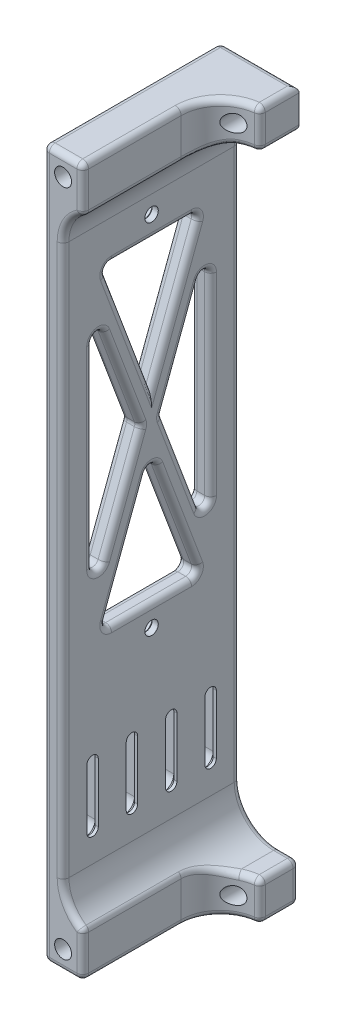
SolidWorks part; units mm, degrees
ref_plane "Front Plane" through (0, 0, 0) normal (0, 0, 1) x (1, 0, 0)
ref_plane "Top Plane" through (0, 0, 0) normal (0, 1, 0) x (1, 0, 0)
ref_plane "Right Plane" through (0, 0, 0) normal (1, 0, 0) x (0, 0, -1)
sketch "Sketch1" plane through (0, 0, 0) normal (1, 0, 0) x (0, 0, -1)
  line L1 (0, 0) -> (45, 0)
  line L2 (0, 0) -> (0, 180)
  line L3 (0, 180) -> (45, 180)
  line L4 (45, 0) -> (45, 180)
  dimension "D1" = 45
  dimension "D2" = 180
extrude "Boss-Extrude1" add sketch "Sketch1" along normal blind 10
sketch "Sketch2" plane through (10, 0, 0) normal (1, 0, 0) x (0, 0, -1)
  line L0 (0, 110) -> (45, 110) construction
  line L1 (0, 0) -> (45, 0) construction
  line L3 (22.5, 64.5) -> (22.5, 155.5) construction
  line L4 (0, 180) -> (0, 0) construction
  line L5 (45, 0) -> (45, 180) construction
  line L6 (27.5, 110) -> (17.5, 110) construction
  point P7 (22.5, 155.5)
  point P8 (22.5, 64.5)
  point P9 (22.5, 110)
  dimension "D1" = 91
  dimension "D2" = 110
  dimension "D3" = 10
hole_wizard "M3 Clearance Hole1" positions "Sketch2" profile "Sketch4" hole size "M3" standard "ANSI Metric"
sketch "Sketch4" plane through (10, 64.5, -22.5) normal (0, 1, 0) x (0, 0, -1)
  line L0 (0, 0) -> (0, 10)
  line L1 (0, 10) -> (1.7, 10)
  line L2 (1.7, 10) -> (1.7, 0)
  line L5 (1.7, 0) -> (0, 0)
  line L11 (0, -6.35) -> (0, 107.95) construction
  dimension "Thru Hole Dia." = 3.4
  dimension "Thru Hole Depth" = 10
sketch "Sketch5" plane through (10, 0, 0) normal (1, 0, 0) x (0, 0, -1)
  line L0 (45, 180) -> (0, 180) construction
  line L1 (45, 180) -> (35, 180)
  line L2 (45, 180) -> (45, 170)
  line L3 (45, 170) -> (35, 170)
  line L4 (35, 180) -> (35, 170)
  line L5 (0, 180) -> (10, 180)
  line L6 (0, 180) -> (0, 170)
  line L7 (0, 170) -> (10, 170)
  line L8 (10, 180) -> (10, 170)
  line L9 (0, 0) -> (45, 0) construction
  line L10 (0, 0) -> (10, 0)
  line L11 (0, 0) -> (0, 10)
  line L12 (0, 10) -> (10, 10)
  line L13 (10, 0) -> (10, 10)
  line L14 (45, 0) -> (35, 0)
  line L15 (45, 0) -> (45, 10)
  line L16 (45, 10) -> (35, 10)
  line L17 (35, 0) -> (35, 10)
  line L18 (45, 0) -> (45, 180) construction
  line M18 (0, 0) -> (45, 0)
  line M19 (45, 0) -> (45, 180)
  line M20 (45, 180) -> (0, 180)
  dimension "D1" = 10
  dimension "D2" = 10
  dimension "D3" = 10
  dimension "D4" = 10
  dimension "D5" = 10
  dimension "D6" = 10
  dimension "D7" = 10
  dimension "D8" = 10
extrude "Boss-Extrude2" add sketch "Sketch5" along normal blind 10 contours L4 L3 M20 M19 | L17 L16 M18 M19
fillet "Fillet1" radius 10 2 edges at (10, 5, -35) (10, 175, -35)
sketch "Sketch7" plane through (0, 0, -45) normal (0, 0, -1) x (-1, 0, 0)
  line L0 (-15, 175) -> (-5, 175) construction
  line L1 (-5, 175) -> (-5, 5) construction
  line L2 (-5, 5) -> (-15, 5) construction
  line L4 (0, 0) -> (0, 180) construction
  line L5 (-20, 10) -> (-10, 10) construction
  line L7 (-20, 180) -> (0, 180) construction
  line L8 (-20, 0) -> (-20, 10) construction
  line L9 (-20, 170) -> (-20, 180) construction
  point P0 (-15, 175)
  point P1 (-5, 175)
  point P3 (-5, 5)
  point P4 (-15, 5)
  dimension "D1" = 5
  dimension "D2" = 5
  dimension "D3" = 5
  dimension "D4" = 5
  dimension "D5" = 5
hole_wizard "Ø4.3 (4.3) Diameter Hole1" positions "Sketch7" profile "Sketch8" hole size "Ø4.3" standard "ANSI Metric" end condition through all
sketch "Sketch8" plane through (15, 175, -45) normal (1, 0, 0) x (0, 1, 0)
  line L0 (0, 0) -> (0, 45)
  line L1 (0, 45) -> (2.15, 45)
  line L2 (2.15, 45) -> (2.15, 0)
  line L5 (2.15, 0) -> (0, 0)
  line L11 (0, -6.35) -> (0, 107.95) construction
  dimension "Thru Hole Dia." = 4.3
  dimension "Thru Hole Depth" = 45
sketch "Sketch9" plane through (10, 0, 0) normal (1, 0, 0) x (0, 0, -1)
  line L0 (0, 180) -> (0, 0) construction
  line L1 (0, 170) -> (45, 170)
  line L2 (0, 170) -> (0, 10)
  line L3 (0, 10) -> (45, 10)
  line L4 (45, 170) -> (45, 10)
  line L6 (0, 180) -> (0, 0) construction
  point P6 (0, 166.7431)
  point P9 (0, 0)
  point P11 (45, 170)
  point P13 (0, 0)
  point P14 (45, 10)
extrude "Cut-Extrude1" cut sketch "Sketch9" against normal blind 5
sketch "Sketch10" plane through (5, 0, 0) normal (1, 0, 0) x (0, 0, -1)
  line L0 (0, 110) -> (45, 110) construction
  line L3 (7.5, 150) -> (37.5, 70) construction
  line L4 (7.5, 150) -> (37.5, 150)
  line L5 (7.5, 150) -> (7.5, 70)
  line L6 (7.5, 70) -> (37.5, 70)
  line L7 (37.5, 150) -> (37.5, 70)
  line L8 (7.5, 150) -> (37.5, 70) construction
  line L9 (7.5, 70) -> (37.5, 150) construction
  line L10 (9.8408, 150.8778) -> (39.8408, 70.8778)
  line L11 (5.1592, 149.1222) -> (35.1592, 69.1222)
  line L12 (37.5, 150) -> (7.5, 70) construction
  line L13 (39.8408, 149.1222) -> (9.8408, 69.1222)
  line L14 (35.1592, 150.8778) -> (5.1592, 70.8778)
  line L15 (22.5, 155.5) -> (22.5, 64.5) construction
  arc A0 (9.8408, 150.8778) -> (5.1592, 149.1222) centre (7.5, 150) ccw
  arc A1 (35.1592, 69.1222) -> (39.8408, 70.8778) centre (37.5, 70) ccw
  arc A2 (39.8408, 149.1222) -> (35.1592, 150.8778) centre (37.5, 150) ccw
  arc A3 (5.1592, 70.8778) -> (9.8408, 69.1222) centre (7.5, 70) ccw
  point P2 (22.5, 110)
  point P6 (22.5, 110)
  point P11 (22.5, 110)
  point P16 (22.5, 110)
  dimension "D1" = 30
  dimension "D2" = 80
  dimension "D3" = 5
  dimension "D4" = 5
extrude "Cut-Extrude2" cut sketch "Sketch10" against normal blind 5 contours L14 L4 L10 | L14 L11 L5 | L11 L13 L6 | L7 L13 L10
fillet "Fillet2" radius 10 2 edges at (5, 10, -22.5) (5, 170, -22.5)
sketch "Sketch11" plane through (0, 0, 0) normal (-1, 0, 0) x (0, 0, 1)
  point P0 (-22.5, 155.5)
  point P1 (-22.5, 64.5)
hole_wizard "Ø4.3 (4.3) Diameter Hole2" positions "Sketch11" profile "Sketch12" hole size "Ø4.3" standard "ANSI Metric"
sketch "Sketch12" plane through (0, 155.5, -22.5) normal (0, 1, 0) x (0, 0, 1)
  line L0 (0, 0) -> (0, 3)
  line L1 (0, 3) -> (2.15, 3)
  line L2 (2.15, 3) -> (2.15, 0)
  line L5 (2.15, 0) -> (0, 0)
  line L10 (0, 3) -> (-2.15, 3) construction
  line L11 (0, -6.35) -> (0, 107.95) construction
  dimension "Hole Dia." = 4.3
  dimension "Hole Depth" = 3
  dimension "Drill Angle" = 180
chamfer "Chamfer1" distance 0.45 angle 45 2 edges at (3, 64.5, -24.2) (3, 155.5, -24.2)
sketch "Sketch13" plane through (5, 0, 0) normal (1, 0, 0) x (0, 0, -1)
  line L0 (7.5, 42.5) -> (7.5, 27.5) construction
  line L1 (8.95, 42.5) -> (8.95, 27.5)
  line L2 (6.05, 42.5) -> (6.05, 27.5)
  line L3 (0, 160) -> (0, 20) construction
  line L4 (0, 0) -> (25, 0) construction
  arc A0 (8.95, 42.5) -> (6.05, 42.5) centre (7.5, 42.5) ccw
  arc A1 (6.05, 27.5) -> (8.95, 27.5) centre (7.5, 27.5) ccw
  point P2 (7.5, 35)
  dimension "D1" = 1.45
  dimension "D2" = 15
  dimension "D3" = 7.5
  dimension "D4" = 35
extrude "Cut-Extrude3" cut sketch "Sketch13" against normal blind 5
pattern_linear "LPattern1" count 4 spacing 10 along (0, 0, -1) of "Cut-Extrude3"
sketch "Sketch14" plane through (0, 0, 0) normal (-1, 0, 0) x (0, 0, 1)
  line L9 (-34.85, 27.5) -> (-34.85, 42.5)
  line L10 (-40.15, 42.5) -> (-40.15, 27.5)
  line L11 (-34.85, 27.5) -> (-34.85, 42.5)
  line L12 (-40.15, 42.5) -> (-40.15, 27.5)
  arc A5 (-40.15, 27.5) -> (-34.85, 27.5) centre (-37.5, 27.5) ccw
  arc A6 (-34.85, 42.5) -> (-40.15, 42.5) centre (-37.5, 42.5) ccw
  arc A7 (-40.15, 27.5) -> (-34.85, 27.5) centre (-37.5, 27.5) ccw
  arc A8 (-34.85, 42.5) -> (-40.15, 42.5) centre (-37.5, 42.5) ccw
  dimension "D1" = 1.2
extrude "Cut-Extrude4" cut sketch "Sketch14" against normal blind 3
pattern_linear "LPattern2" count 4 spacing 10 along (0, 0, 1) of "Cut-Extrude4"
chamfer "Chamfer2" distance 1.2 angle 45 16 edges at (3, 35, -6.05) (3, 26.05, -7.5) (3, 43.95, -7.5) (3, 35, -8.95) (3, 35, -16.05) (3, 26.05, -17.5) (3, 43.95, -17.5) (3, 35, -18.95) (3, 35, -26.05) (3, 26.05, -27.5) (3, 43.95, -27.5) (3, 35, -28.95) (3, 35, -36.05) (3, 26.05, -37.5) (3, 43.95, -37.5) (3, 35, -38.95)
fillet "Fillet3" radius 1.5 69 edges at (10, 5.6699, 0) (5, 86.44, -28.665) (2.5, 102.88, -22.5) (0, 70, -22.5) (2.5, 70, -34.83) (0, 86.44, -16.335) (2.5, 70, -10.17) (0, 86.44, -28.665) (5, 86.44, -16.335) (5, 70, -22.5) (5, 93.56, -13.665) (2.5, 110, -19.83) (0, 110, -7.5) (2.5, 77.12, -7.5) (5, 126.44, -13.665) (2.5, 142.88, -7.5) (0, 93.56, -13.665) (0, 126.44, -13.665) (5, 110, -7.5) (5, 110, -37.5) (2.5, 142.88, -37.5) (0, 93.56, -31.335) (2.5, 77.12, -37.5) (0, 126.44, -31.335) (2.5, 110, -25.17) (0, 110, -37.5) (5, 126.44, -31.335) (5, 93.56, -31.335) (5, 133.56, -28.665) (2.5, 150, -34.83) (0, 133.56, -16.335) (5, 150, -22.5) (2.5, 150, -10.17) (0, 133.56, -28.665) (0, 150, -22.5) (5, 133.56, -16.335) (5, 90, 0) (5, 90, -45) (17.4118, 10, -34.6593) (7.9289, 12.9289, -45) (10.8596, 10.8974, -29.0563) (10, 11.3397, -12.5) (6.3397, 15, 0) (6.3397, 165, 0) (10, 168.6603, -12.5) (11.9278, 169.5164, -30.9025) (7.9289, 167.0711, -45) (20, 170, -40) (17.5, 170, -45) (20, 180, -40) (20, 175, -35) (20, 5, -35) (17.5, 10, -45) (20, 0, -40) (20, 10, -40) (10, 174.3301, 0) (0, 180, -22.5) (10, 180, -12.5) (0, 90, -45) (12.9289, 0, -32.0711) (17.4118, 170, -34.6593) (12.9289, 180, -32.0711) (0, 0, -22.5) (0, 90, 0) (5, 180, 0) (10, 180, -45) (10, 0, -45) (5, 0, 0) (10, 0, -12.5)
